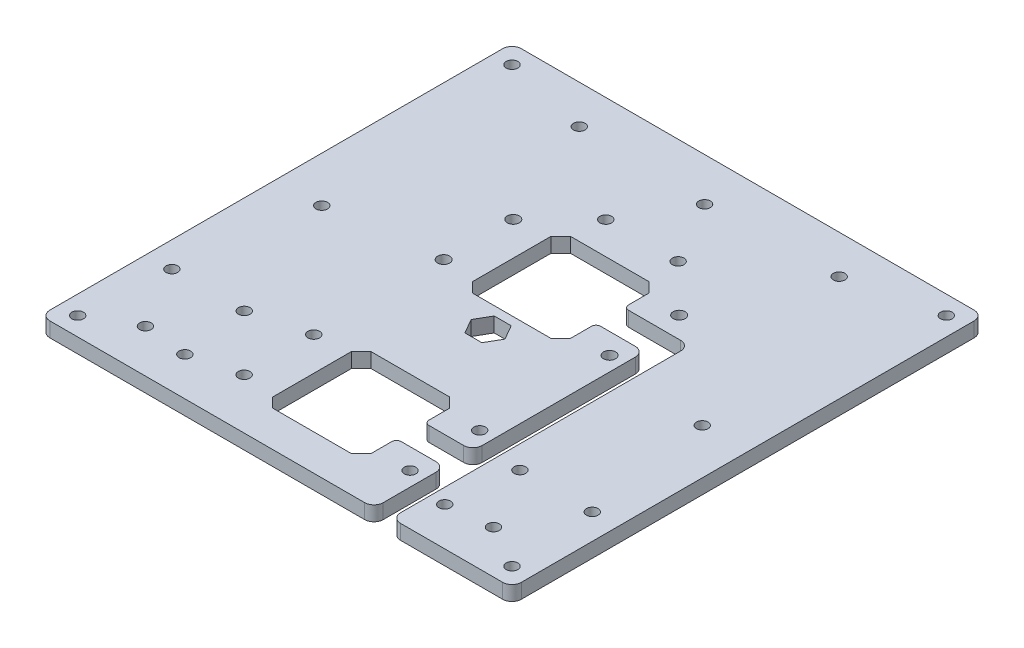
SolidWorks part; units mm, degrees
ref_plane "Plan de face" through (0, 0, 0) normal (0, 0, 1) x (1, 0, 0)
ref_plane "Plan de dessus" through (0, 0, 0) normal (0, 1, 0) x (1, 0, 0)
ref_plane "Plan de droite" through (0, 0, 0) normal (1, 0, 0) x (0, 0, -1)
sketch "Esquisse1" plane through (0, 0, 0) normal (0, 1, 0) x (1, 0, 0)
  line L1 (-101.6, -101.6) -> (101.6, -101.6)
  line L2 (-101.6, -101.6) -> (-101.6, 101.6)
  line L3 (-101.6, 101.6) -> (101.6, 101.6)
  line L4 (101.6, -101.6) -> (101.6, 101.6)
  line L5 (-101.6, -101.6) -> (101.6, 101.6) construction
  line L6 (-101.6, 101.6) -> (101.6, -101.6) construction
  point P0 (0, 0)
  dimension "D1" = 203.2
extrude "Boss.-Extru.1" add sketch "Esquisse1" along normal blind 6.35
sketch "Esquisse2" plane through (0, 6.35, 0) normal (0, 1, 0) x (1, 0, 0)
  circle A0 centre (-35.6, -49.85) radius 2.5
  circle A1 centre (-35.6, -79.85) radius 2.5
  circle A2 centre (35.9, -79.85) radius 2.5
  circle A3 centre (35.9, -49.85) radius 2.5
extrude "Enlèv. mat.-Extru.1" cut sketch "Esquisse2" against normal through all
sketch "Esquisse3" plane through (0, 6.35, 0) normal (0, 1, 0) x (1, 0, 0)
  circle A0 centre (-93.6, 93.6) radius 2.5
  circle A1 centre (93.6, 93.6) radius 2.5
  circle A2 centre (93.6, -93.6) radius 2.5
  circle A3 centre (-93.6, -93.6) radius 2.5
extrude "Enlèv. mat.-Extru.2" cut sketch "Esquisse3" against normal through all
sketch "Esquisse4" plane through (0, 6.35, 0) normal (0, 1, 0) x (1, 0, 0)
  circle A0 centre (15.5885, 56) radius 2.5
  circle A1 centre (-15.5885, 56) radius 2.5
  circle A2 centre (0, 83) radius 2.5
  circle A3 centre (-75, -83) radius 2.5
  circle A4 centre (-90.5885, -56) radius 2.5
  circle A5 centre (-59.4115, -56) radius 2.5
  circle A6 centre (59.413, -55.9992) radius 2.5
  circle A7 centre (90.5899, -55.9992) radius 2.5
  circle A8 centre (75.0015, -82.9992) radius 2.5
extrude "Enlèv. mat.-Extru.3" cut sketch "Esquisse4" against normal through all
sketch "Esquisse6" plane through (0, 0, 0) normal (0, -1, 0) x (1, 0, 0)
  line L0 (-56, 85) -> (-56, -85) construction
  circle A0 centre (-56, 85) radius 2.5
  circle A1 centre (-56, -85) radius 2.5
  circle A2 centre (-82, 0) radius 2.5
  point P6 (-56, 0)
  dimension "D1" = 5
  dimension "D2" = 82
  dimension "D3" = 85
  dimension "D4" = 56
extrude "Enlèv. mat.-Extru.5" cut sketch "Esquisse6" against normal through all
mirror "Symétrie1" about plane through (0, 0, 0) normal (1, 0, 0) of "Enlèv. mat.-Extru.5"
sketch "Esquisse8" plane through (0, 6.35, 0) normal (0, 1, 0) x (1, 0, 0)
  circle A0 centre (75, -65) radius 3.925
  circle A1 centre (75, -65) radius 3.925 construction
sketch "Esquisse11" plane through (0, 6.35, 0) normal (0, 1, 0) x (1, 0, 0)
  line L0 (-16.9781, 42.15) -> (16.9781, 42.15)
  line L1 (16.9781, 42.15) -> (21.15, 37.9781)
  line L2 (21.15, 37.9781) -> (21.15, 4.0219)
  line L3 (21.15, 4.0219) -> (16.9781, -0.15)
  line L4 (16.9781, -0.15) -> (-16.9781, -0.15)
  line L5 (-16.9781, -0.15) -> (-21.15, 4.0219)
  line L6 (-21.15, 4.0219) -> (-21.15, 37.9781)
  line L7 (-21.15, 37.9781) -> (-16.9781, 42.15)
  line L8 (21.15, 4.0219) -> (21.15, 37.9781) construction
  line L9 (-21.15, 4.0219) -> (-16.9781, -0.15) construction
  line L10 (-21.15, 37.9781) -> (-21.15, 4.0219) construction
  line L11 (-16.9781, 42.15) -> (-21.15, 37.9781) construction
extrude "Enlèv. mat.-Extru.9" cut sketch "Esquisse11" against normal through all
sketch "Esquisse5" plane through (0, 6.35, 0) normal (0, 1, 0) x (1, 0, 0)
  line L0 (101.6, 101.6) -> (-101.6, 101.6) construction
  line L1 (3.6517, -4) -> (-3.6517, -4)
  line L2 (-3.6517, -4) -> (-7.3035, -10.325)
  line L3 (-7.3035, -10.325) -> (-3.6517, -16.65)
  line L4 (-3.6517, -16.65) -> (3.6517, -16.65)
  line L5 (3.6517, -16.65) -> (7.3035, -10.325)
  line L6 (7.3035, -10.325) -> (3.6517, -4)
  circle A0 centre (0, -10.325) radius 6.325 construction
  dimension "D1" = 12.65
  dimension "D2" = 4
extrude "Enlèv. mat.-Extru.4" cut sketch "Esquisse5" against normal through all
sketch "Esquisse9" plane through (0, 6.35, 0) normal (0, 1, 0) x (1, 0, 0)
  line L0 (-16.9781, -43.85) -> (16.9781, -43.85)
  line L1 (16.9781, -43.85) -> (21.15, -48.0219)
  line L2 (21.15, -48.0219) -> (21.15, -81.9781)
  line L3 (21.15, -81.9781) -> (16.9781, -86.15)
  line L4 (16.9781, -86.15) -> (-16.9781, -86.15)
  line L5 (-16.9781, -86.15) -> (-21.15, -81.9781)
  line L6 (-21.15, -81.9781) -> (-21.15, -48.0219)
  line L7 (-21.15, -48.0219) -> (-16.9781, -43.85)
  point P4 (21.15, -65)
  point P9 (-21.15, -65)
  point P12 (0, -43.85)
  point P13 (0, -86.15)
  dimension "D1" = 5.9
  dimension "D2" = 42.3
  dimension "D3" = 42.3
extrude "Enlèv. mat.-Extru.7" cut sketch "Esquisse9" against normal through all
sketch "Esquisse10" plane through (0, 6.35, 0) normal (0, 1, 0) x (1, 0, 0)
  line L0 (21.15, -81.9781) -> (21.15, -48.0219) construction
  line L1 (21.15, -58.9281) -> (42.1, -58.9281)
  line L2 (21.15, -58.9281) -> (21.15, -70.9281)
  line L3 (21.15, -70.9281) -> (42.1, -70.9281)
  line L4 (49.6, -58.9281) -> (49.6, -70.9281)
  line L5 (-101.6, -101.6) -> (101.6, -101.6) construction
  line L7 (49.6, -70.9281) -> (49.6, -101.6)
  line L8 (49.6, -101.6) -> (42.1, -101.6)
  line L9 (42.1, -70.9281) -> (42.1, -101.6)
  line L10 (101.6, -101.6) -> (101.6, 101.6) construction
  line L11 (21.15, 4.0219) -> (21.15, 37.9781) construction
  line L12 (21.15, 15.0719) -> (42.1, 15.0719)
  line L13 (21.15, 15.0719) -> (21.15, 27.0719)
  line L14 (21.15, 27.0719) -> (49.6, 27.0719)
  line L15 (49.6, 15.0719) -> (49.6, 27.0719)
  line L18 (49.6, 15.0719) -> (49.6, -58.9281)
  line L20 (42.1, 15.0719) -> (42.1, -58.9281)
  dimension "D1" = 11.05
  dimension "D2" = 12
  dimension "D3" = 7.5
  dimension "D4" = 52
  dimension "D5" = 11.05
extrude "Enlèv. mat.-Extru.8" cut sketch "Esquisse10" against normal through all
fillet "Congé3" radius 2 4 edges at (21.15, 3.175, 70.9281) (21.15, 3.175, 58.9281) (21.15, 3.175, -15.0719) (21.15, 3.175, -27.0719)
fillet "Congé2" radius 4 10 edges at (101.6, 3.175, -101.6) (-101.6, 3.175, -101.6) (-101.6, 3.175, 101.6) (101.6, 3.175, 101.6) (42.1, 3.175, 70.9281) (49.6, 3.175, 101.6) (42.1, 3.175, 101.6) (42.1, 3.175, 58.9281) (42.1, 3.175, -15.0719) (49.6, 3.175, -27.0719)
sketch "Esquisse12" plane through (0, 6.35, 0) normal (0, 1, 0) x (1, 0, 0)
  circle A0 centre (-35.6, 36.15) radius 2.6
  circle A1 centre (-35.6, 6.15) radius 2.6
  circle A2 centre (35.9, 6.15) radius 2.6
  circle A3 centre (35.9, 36.15) radius 2.6
  circle A4 centre (35.9, 36.15) radius 2.6 construction
extrude "Enlèv. mat.-Extru.10" cut sketch "Esquisse12" against normal through all
equation "\"grosseur_nut_longue_screw\"=12.65"
equation "\"D1@Esquisse5\"=\"grosseur_nut_longue_screw\""
